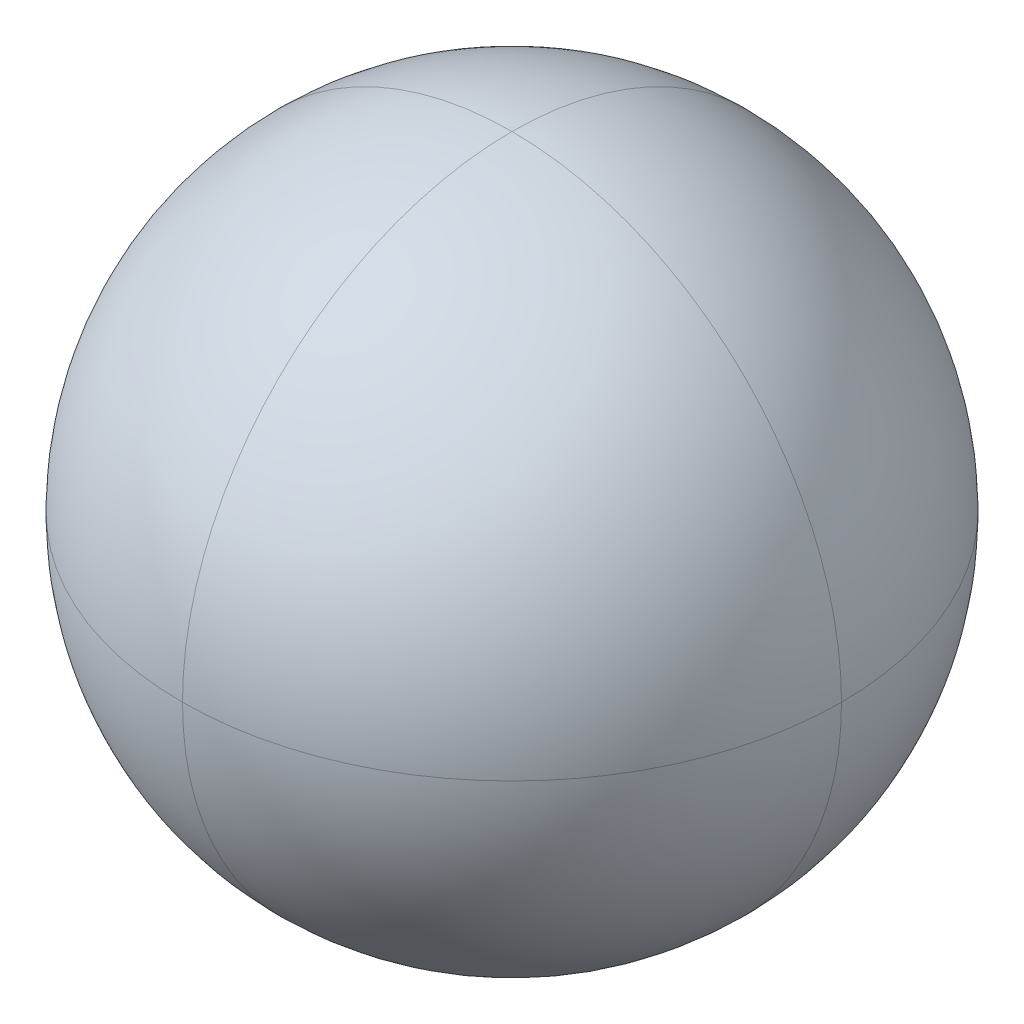
SolidWorks part; units mm, degrees
ref_plane "Front Plane" through (0, 0, 0) normal (0, 0, 1) x (1, 0, 0)
ref_plane "Top Plane" through (0, 0, 0) normal (0, 1, 0) x (1, 0, 0)
ref_plane "Right Plane" through (0, 0, 0) normal (1, 0, 0) x (0, 0, -1)
sketch "Sketch7" plane through (0, 0, 0) normal (0, 1, 0) x (1, 0, 0)
  line L1 (-20, 20) -> (20, 20)
  line L2 (-20, 20) -> (-20, -20)
  line L3 (-20, -20) -> (20, -20)
  line L4 (20, 20) -> (20, -20)
  line L5 (-20, 20) -> (20, -20) construction
  line L6 (-20, -20) -> (20, 20) construction
  point P0 (0, 0)
extrude "Boss-Extrude1" add sketch "Sketch7" along normal blind 40
fillet "Fillet1" radius 20 6 edges at (20, 0, 0) (0, 0, 20) (0, 40, -20) (-20, 40, 0) (-20, 20, 20) (20, 20, -20)
